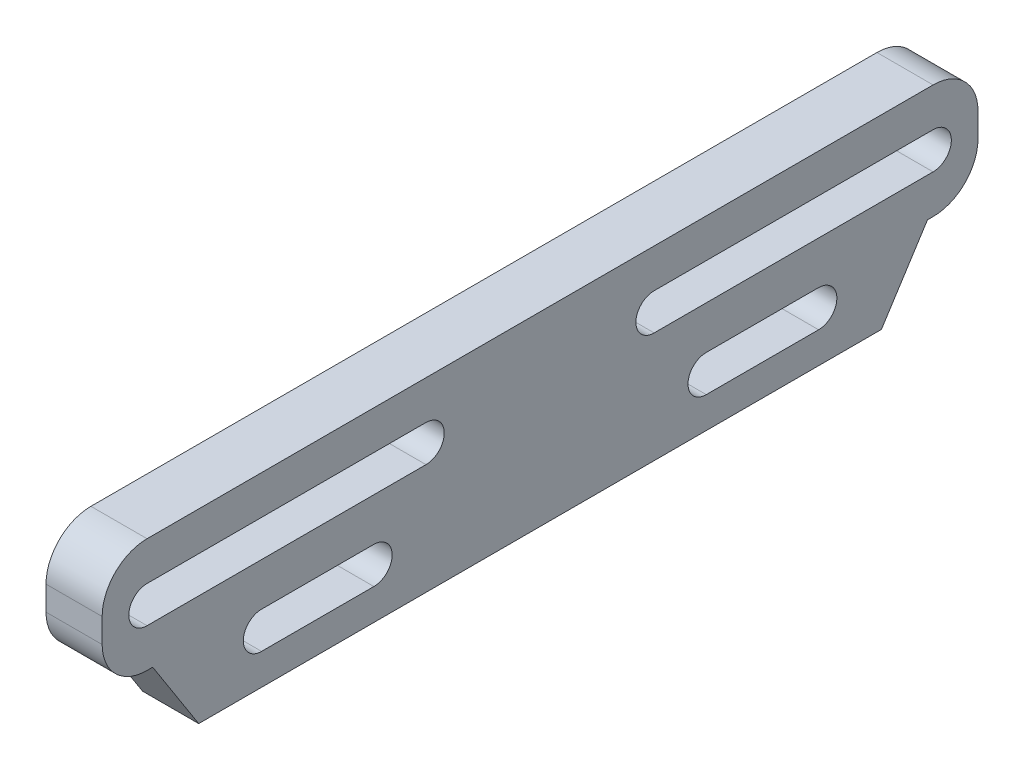
SolidWorks part; units mm, degrees
ref_plane "Plan de face" through (0, 0, 0) normal (0, 0, 1) x (1, 0, 0)
ref_plane "Plan de dessus" through (0, 0, 0) normal (0, 1, 0) x (1, 0, 0)
ref_plane "Plan de droite" through (0, 0, 0) normal (1, 0, 0) x (0, 0, -1)
sketch "Esquisse1" plane through (0, 0, 0) normal (0, 0, 1) x (1, 0, 0)
  line L1 (0, 0) -> (12.5, 0)
  line L2 (0, 0) -> (0, 25.4)
  line L3 (0, 25.4) -> (12.5, 25.4)
  line L4 (12.5, 0) -> (12.5, 25.4)
  dimension "D1" = 12.5
  dimension "D2" = 25.4
extrude "Boss.-Extru.1" add sketch "Esquisse1" along normal blind 97.5 and the other way blind 97.5
sketch "Esquisse3" plane through (0, 0, 0) normal (-1, 0, 0) x (0, 0, 1)
  line L0 (25.4, 12.7) -> (87.5, 12.7) construction
  line L1 (25.4, 16.765) -> (87.5, 16.765)
  line L2 (25.4, 8.635) -> (87.5, 8.635)
  line L3 (0, -55) -> (0, 55) construction
  line L4 (97.5, 25.4) -> (97.5, 0) construction
  arc A0 (25.4, 16.765) -> (25.4, 8.635) centre (25.4, 12.7) ccw
  arc A1 (87.5, 8.635) -> (87.5, 16.765) centre (87.5, 12.7) ccw
  point P2 (56.45, 12.7)
  point P11 (97.5, 12.7)
  dimension "D1" = 25.4
  dimension "D2" = 10
  dimension "D3" = 8.13
extrude "Enlèv. mat.-Extru.1" cut sketch "Esquisse3" against normal through all
mirror "Symétrie1" about plane through (0, 0, 0) normal (0, 0, 1) of "Enlèv. mat.-Extru.1"
fillet "Congé1" radius 10 1 edges at (6.25, 0, -97.5) type face fillet first side face at (6.25, 12.7, -97.5) second side face at (6.25, 0, 0)
fillet "Congé2" radius 10 1 edges at (6.25, 25.4, -97.5) type face fillet first side face at (6.25, 17.7, -97.5) second side face at (6.25, 25.4, 0)
fillet "Congé3" radius 10 1 edges at (6.25, 0, 97.5) type face fillet first side face at (6.25, 12.7, 97.5) second side face at (6.25, 0, 5)
fillet "Congé4" radius 10 1 edges at (6.25, 25.4, 97.5) type face fillet first side face at (6.25, 25.4, 5) second side face at (6.25, 17.7, 97.5)
sketch "Esquisse4" plane through (12.5, 0, 0) normal (1, 0, 0) x (0, 0, -1)
  line L0 (87.5, 0) -> (-87.5, 0) construction
  line L1 (0, 0) -> (-56.5663, 0)
  line L3 (0, -16) -> (-76, -16)
  line L5 (-76, -16) -> (-86.247, 0)
  line L6 (0, 0) -> (56.5663, 0)
  line L8 (0, -16) -> (76, -16)
  line L10 (76, -16) -> (86.247, 0)
  line L11 (-86.247, 0) -> (-56.5663, 0)
  line L12 (56.5663, 0) -> (86.247, 0)
  dimension "D1" = 76
  dimension "D2" = 16
  dimension "D3" = 19
extrude "Boss.-Extru.4" add sketch "Esquisse4" against normal up to surface (12.5 mm away) up to face at (0, 12.7, 56.45)
sketch "Esquisse5" plane through (12.5, 0, 0) normal (1, 0, 0) x (0, 0, -1)
  line L0 (-62.01, -5) -> (-37, -5) construction
  line L1 (-62.01, -0.935) -> (-37, -0.935)
  line L2 (-62.01, -9.065) -> (-37, -9.065)
  arc A0 (-62.01, -0.935) -> (-62.01, -9.065) centre (-62.01, -5) ccw
  arc A1 (-37, -9.065) -> (-37, -0.935) centre (-37, -5) ccw
  point P2 (-49.505, -5)
  point P17 (-66.075, -5)
  point P18 (-32.935, -5)
  dimension "D1" = 8.13
  dimension "D2" = 5
  dimension "D3" = 37
  dimension "D5" = 33.14
extrude "Enlèv. mat.-Extru.2" cut sketch "Esquisse5" against normal through all
mirror "Symétrie2" about plane through (0, 0, 0) normal (0, 0, 1) of "Enlèv. mat.-Extru.2"
